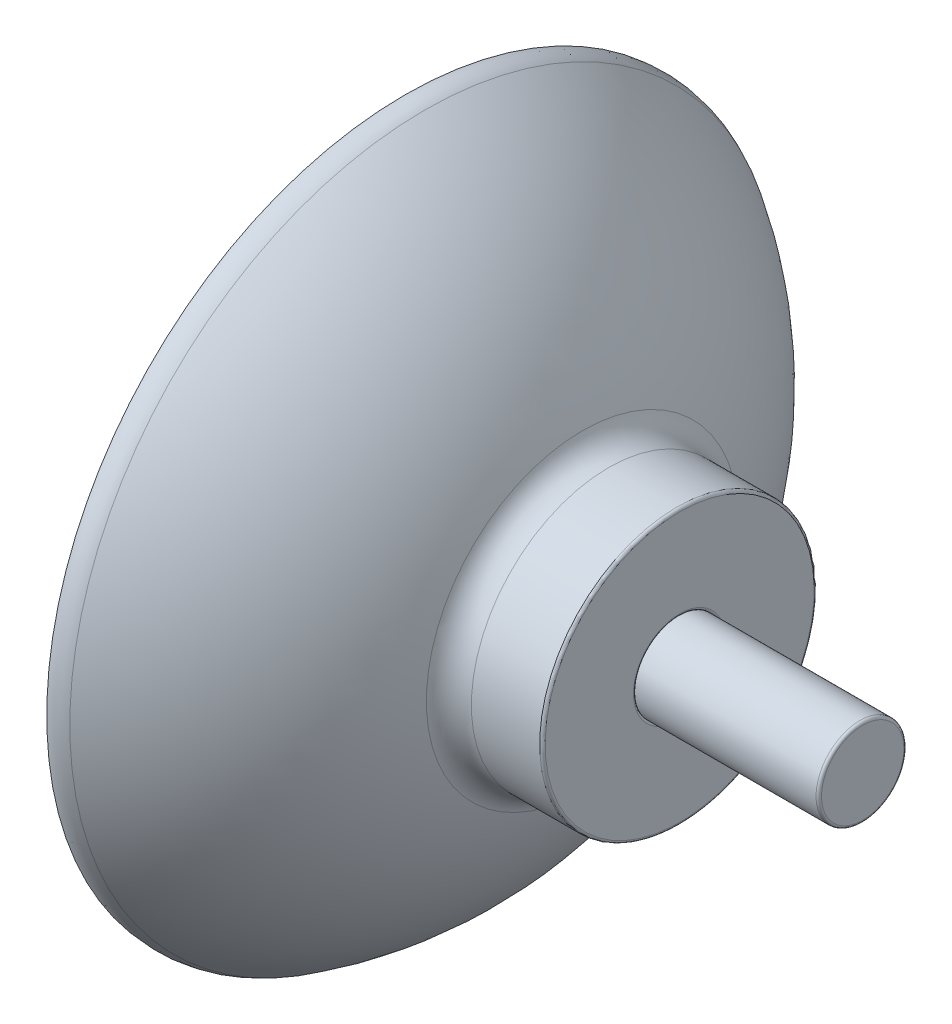
SolidWorks part; units mm, degrees
material "Malleable Cast Iron"
ref_plane "Front Plane" through (0, 0, 0) normal (0, 0, 1) x (1, 0, 0)
ref_plane "Top Plane" through (0, 0, 0) normal (0, 1, 0) x (1, 0, 0)
ref_plane "Right Plane" through (0, 0, 0) normal (1, 0, 0) x (0, 0, -1)
sketch "Sketch1" plane through (0, 0, 0) normal (0, 0, 1) x (1, 0, 0)
  line L0 (0, 0) -> (-10, 0) construction
  line L1 (0, 0) -> (5, 0) construction
  line L2 (0, 0) -> (0, 7.5)
  line L3 (0, 7.5) -> (5, 7.5)
  line L4 (5, 0) -> (5, 7.5)
  line L5 (2, 0) -> (4, 0) construction
  line L6 (2, 0) -> (2, 4.75)
  line L7 (2, 4.75) -> (4, 4.75)
  line L8 (4, 0) -> (4, 4.75)
  line L9 (-10, 0) -> (-10, 20) construction
  line L10 (-10, 20) -> (-10, 19.5)
  line L11 (5, 0) -> (4, 0)
  line L12 (2, 0) -> (0, 0)
  line L13 (4, 2.375) -> (5, 2.375)
  arc A0 (0, 7.5) -> (-10, 20) centre (-19.3122, 2.3002) ccw
  arc A1 (-10, 19.5) -> (0, 4) centre (-21.7836, 0.9219) cw
  dimension "D8" = 20
  dimension "D11" = 22
  dimension "D1" = 5
  dimension "D2" = 2
  dimension "D3" = 1
  dimension "D4" = 7.5
  dimension "D5" = 4.75
  dimension "D6" = 20
  dimension "D7" = 10
  dimension "D9" = 0.5
  dimension "D10" = 3.5
revolve "Revolve1" add sketch "Sketch1" angle 360 about L0 region at (0.0901, 2, 0) region at (-3.1385, 12.951, 0)
fillet "Fillet1" radius 0.15 5 edges at (4, 2.375, 0) (5, 2.375, 0) (5, 7.5, 0) (-10, 19.5, 0) (0, 4, 0)
fillet "Fillet2" radius 1.5 2 edges at (0, 7.5, 0) (-10, 20, 0)
sketch "Sketch2" plane through (0, 0, 0) normal (0, 0, 1) x (1, 0, 0)
  line L0 (2, 0) -> (2, 4.75)
  line L1 (2, -4.75) -> (2, 4.75) construction
  line L2 (2, 4.75) -> (4, 4.75)
  line L3 (4, 4.75) -> (4, -4.75) construction
  line L4 (4, 4.75) -> (4, 2.4)
  line L5 (4, 2.4) -> (15, 2.4)
  line L6 (15, 2.4) -> (15, 0)
  line L7 (15, 0) -> (2, 0)
  dimension "D1" = 11
  dimension "D2" = 2.35
  dimension "D3" = 2.4
revolve "Revolve2" add sketch "Sketch2" angle 360 about L7
fillet "Fillet3" radius 0.15 1 edges at (15, 0, -2.4)
